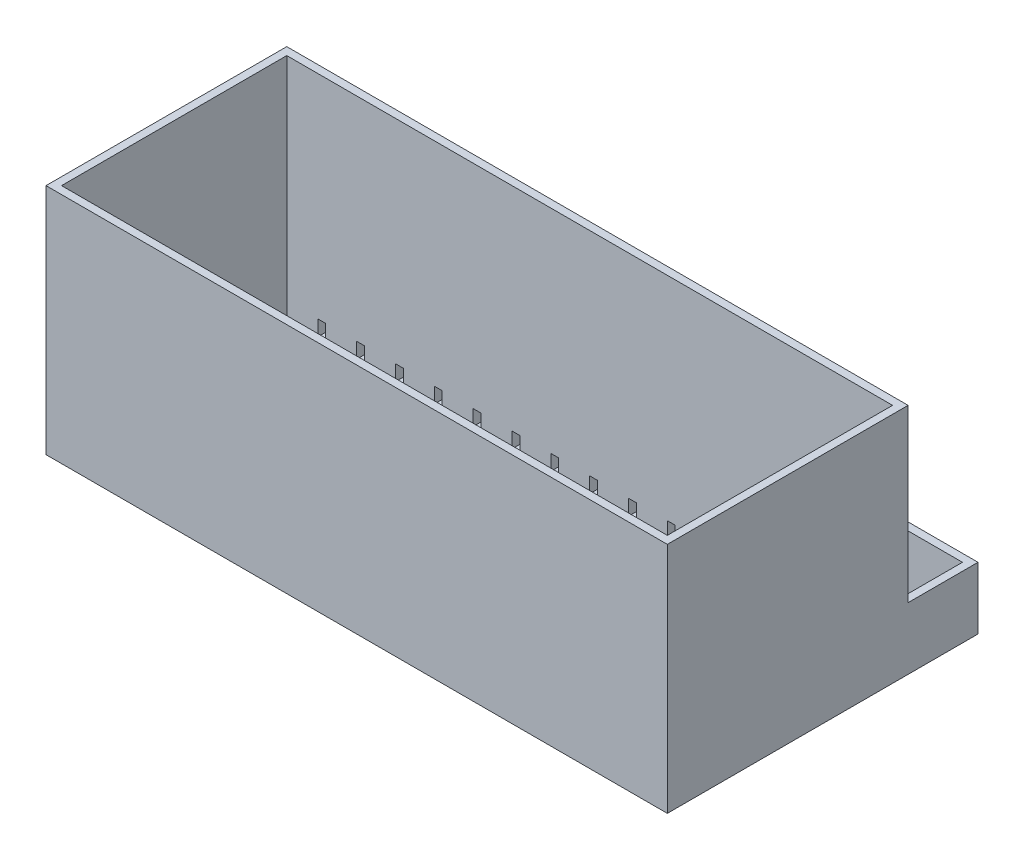
SolidWorks part; units mm, degrees
ref_plane "Front Plane" through (0, 0, 0) normal (0, 0, 1) x (1, 0, 0)
ref_plane "Top Plane" through (0, 0, 0) normal (0, 1, 0) x (1, 0, 0)
ref_plane "Right Plane" through (0, 0, 0) normal (1, 0, 0) x (0, 0, -1)
sketch "Sketch1" plane through (0, 0, 0) normal (0, 1, 0) x (1, 0, 0)
  line L0 (100, 0) -> (100, 75) construction
  line L1 (0, 0) -> (200, 0)
  line L2 (0, 0) -> (0, 77.5)
  line L3 (0, 77.5) -> (200, 77.5)
  line L4 (200, 0) -> (200, 77.5)
  line L5 (2.5, 75) -> (197.5, 75)
  line L6 (2.5, 75) -> (2.5, 2.5)
  line L7 (2.5, 2.5) -> (197.5, 2.5)
  line L8 (197.5, 75) -> (197.5, 2.5)
  line L9 (15, 75) -> (15, 77.5)
  line L10 (0, 77.5) -> (200, 77.5)
  line L11 (0, 77.5) -> (0, 100)
  line L12 (0, 100) -> (200, 100)
  line L13 (200, 77.5) -> (200, 100)
  line L14 (2.5, 75) -> (197.5, 75)
  line L15 (2.5, 75) -> (2.5, 97.5)
  line L16 (2.5, 97.5) -> (197.5, 97.5)
  line L17 (197.5, 75) -> (197.5, 97.5)
  line L18 (2.5, 75) -> (12.5, 75)
  line L19 (2.5, 75) -> (2.5, 77.5)
  line L20 (2.5, 77.5) -> (12.5, 77.5)
  line L21 (12.5, 75) -> (12.5, 77.5)
  line L22 (27.5, 75) -> (27.5, 77.5)
  line L23 (25, 75) -> (25, 77.5)
  line L24 (40, 75) -> (40, 77.5)
  line L25 (37.5, 75) -> (37.5, 77.5)
  line L26 (52.5, 75) -> (52.5, 77.5)
  line L27 (50, 75) -> (50, 77.5)
  line L28 (65, 75) -> (65, 77.5)
  line L29 (62.5, 75) -> (62.5, 77.5)
  line L30 (77.5, 75) -> (77.5, 77.5)
  line L31 (75, 75) -> (75, 77.5)
  line L32 (90, 75) -> (90, 77.5)
  line L33 (87.5, 75) -> (87.5, 77.5)
  line L34 (102.5, 75) -> (102.5, 77.5)
  line L35 (100, 75) -> (100, 77.5)
  line L36 (115, 75) -> (115, 77.5)
  line L37 (112.5, 75) -> (112.5, 77.5)
  line L38 (127.5, 75) -> (127.5, 77.5)
  line L39 (125, 75) -> (125, 77.5)
  line L40 (140, 75) -> (140, 77.5)
  line L41 (137.5, 75) -> (137.5, 77.5)
  line L42 (152.5, 75) -> (152.5, 77.5)
  line L43 (150, 75) -> (150, 77.5)
  line L44 (165, 75) -> (165, 77.5)
  line L45 (162.5, 75) -> (162.5, 77.5)
  line L46 (177.5, 75) -> (177.5, 77.5)
  line L47 (175, 75) -> (175, 77.5)
  line L48 (190, 75) -> (190, 77.5)
  line L49 (187.5, 75) -> (187.5, 77.5)
  point P16 (25.7087, 75)
  dimension "D1" = 2.5
  dimension "D2" = 2.5
  dimension "D3" = 200
  dimension "D4" = 100
  dimension "D5" = 2.5
  dimension "D6" = 2.5
  dimension "D7" = 20
  dimension "D8" = 10
  dimension "D9" = 2.5
  dimension "D11" = 10
  dimension "D10" = 15
extrude "Boss-Extrude1" add sketch "Sketch1" along normal blind 1.6 contours L7 L0 L5 L14 L6 | L0 L7 L8 L5 L14 | L5 L21 L10 L15 | L21 L14 L9 L3 | L5 L23 L3 L9 | L23 L14 L22 L10 | L14 L25 L10 L22 | L25 L5 L24 L3 | L5 L27 L3 L24 | L27 L14 L26 L10 | L14 L29 L10 L26 | L29 L5 L28 L3 | L5 L31 L3 L28 | L31 L14 L30 L10 | L14 L33 L10 L30 | L33 L5 L32 L3 | L5 L35 L3 L32 | L35 L14 L34 L10 | L14 L37 L10 L34 | L37 L5 L36 L3 | L5 L39 L3 L36 | L39 L14 L38 L10 | L14 L41 L10 L38 | L41 L5 L40 L3 | L5 L43 L3 L40 | L43 L14 L42 L10 | L14 L45 L10 L42 | L45 L5 L44 L3 | L5 L47 L3 L44 | L47 L14 L46 L10 | L14 L49 L10 L46 | L49 L5 L48 L3 | L48 L5 L17 L3 | L3 L10 L17 L16 L15 L8 region at (51.25, 0, -38.75) region at (148.75, 0, -38.75) region at (101.25, 0, -76.25) region at (95, 0, -76.25) region at (88.75, 0, -76.25) region at (107.5, 0, -76.25) region at (100, 0, -87.5) region at (7.5, 0, -76.25) region at (193.75, 0, -76.25) region at (82.5, 0, -76.25) region at (113.75, 0, -76.25) region at (13.75, 0, -76.25) region at (188.75, 0, -76.25) region at (76.25, 0, -76.25) region at (120, 0, -76.25) region at (20, 0, -76.25) region at (182.5, 0, -76.25) region at (70, 0, -76.25) region at (126.25, 0, -76.25) region at (26.25, 0, -76.25) region at (176.25, 0, -76.25) region at (63.75, 0, -76.25) region at (132.5, 0, -76.25) region at (32.5, 0, -76.25) region at (170, 0, -76.25) region at (57.5, 0, -76.25) region at (138.75, 0, -76.25) region at (38.75, 0, -76.25) region at (163.75, 0, -76.25) region at (51.25, 0, -76.25) region at (145, 0, -76.25) region at (45, 0, -76.25) region at (157.5, 0, -76.25) region at (151.25, 0, -76.25)
extrude "Boss-Extrude2" add sketch "Sketch1<5>" along normal blind 75 contours L1 L0 L7 L6 L15 L3 L2 | L0 L1 L4 L10 L17 L8 L7 | L48 L5 L17 L3 | L49 L5 L48 L3 | L14 L49 L10 L46 | L47 L14 L46 L10 | L5 L47 L3 L44 | L45 L5 L44 L3 | L14 L45 L10 L42 | L43 L14 L42 L10 | L5 L43 L3 L40 | L41 L5 L40 L3 | L14 L41 L10 L38 | L39 L14 L38 L10 | L5 L39 L3 L36 | L37 L5 L36 L3 | L14 L37 L10 L34 | L35 L14 L34 L10 | L5 L35 L3 L32 | L33 L5 L32 L3 | L14 L33 L10 L30 | L31 L14 L30 L10 | L5 L31 L3 L28 | L29 L5 L28 L3 | L14 L29 L10 L26 | L27 L14 L26 L10 | L5 L27 L3 L24 | L25 L5 L24 L3 | L14 L25 L10 L22 | L23 L14 L22 L10 | L5 L23 L3 L9 | L21 L14 L9 L3 | L5 L21 L10 L15 region at (50, 0, -1.2652) region at (101.2652, 0, -1.25) region at (101.25, 0, -76.25) region at (95, 0, -76.25) region at (88.75, 0, -76.25) region at (107.5, 0, -76.25) region at (7.5, 0, -76.25) region at (193.75, 0, -76.25) region at (82.5, 0, -76.25) region at (113.75, 0, -76.25) region at (13.75, 0, -76.25) region at (188.75, 0, -76.25) region at (76.25, 0, -76.25) region at (120, 0, -76.25) region at (20, 0, -76.25) region at (182.5, 0, -76.25) region at (70, 0, -76.25) region at (126.25, 0, -76.25) region at (26.25, 0, -76.25) region at (176.25, 0, -76.25) region at (63.75, 0, -76.25) region at (132.5, 0, -76.25) region at (32.5, 0, -76.25) region at (170, 0, -76.25) region at (57.5, 0, -76.25) region at (138.75, 0, -76.25) region at (38.75, 0, -76.25) region at (163.75, 0, -76.25) region at (51.25, 0, -76.25) region at (145, 0, -76.25) region at (45, 0, -76.25) region at (157.5, 0, -76.25) region at (151.25, 0, -76.25)
sketch "Sketch1<5>" plane through (0, 0, 0) normal (0, 1, 0) x (1, 0, 0) same geometry as "Sketch1"
extrude "Boss-Extrude3" add sketch "Sketch1<6>" along normal blind 20 contours L17 L10 L13 L12 L11 L3 L15 L16 region at (2.0126, 0, -88.75)
sketch "Sketch1<6>" plane through (0, 0, 0) normal (0, 1, 0) x (1, 0, 0) same geometry as "Sketch1"
extrude "Cut-Extrude1" cut sketch "Sketch1<7>" along normal blind 5 from surface contours L49 L5 L48 L3 | L47 L14 L46 L10 | L45 L5 L44 L3 | L43 L14 L42 L10 | L41 L5 L40 L3 | L39 L14 L38 L10 | L37 L5 L36 L3 | L35 L14 L34 L10 | L33 L5 L32 L3 | L31 L14 L30 L10 | L29 L5 L28 L3 | L27 L14 L26 L10 | L25 L5 L24 L3 | L23 L14 L22 L10 | L21 L14 L9 L3 region at (13.75, 0, -76.25) region at (188.75, 0, -76.25) region at (26.25, 0, -76.25) region at (176.25, 0, -76.25) region at (38.75, 0, -76.25) region at (163.75, 0, -76.25) region at (51.25, 0, -76.25) region at (151.25, 0, -76.25) region at (63.75, 0, -76.25) region at (138.75, 0, -76.25) region at (76.25, 0, -76.25) region at (126.25, 0, -76.25) region at (88.75, 0, -76.25) region at (113.75, 0, -76.25) region at (101.25, 0, -76.25) starting at face at (100, 1.6, -87.5)
sketch "Sketch1<7>" plane through (0, 0, 0) normal (0, 1, 0) x (1, 0, 0) same geometry as "Sketch1"
